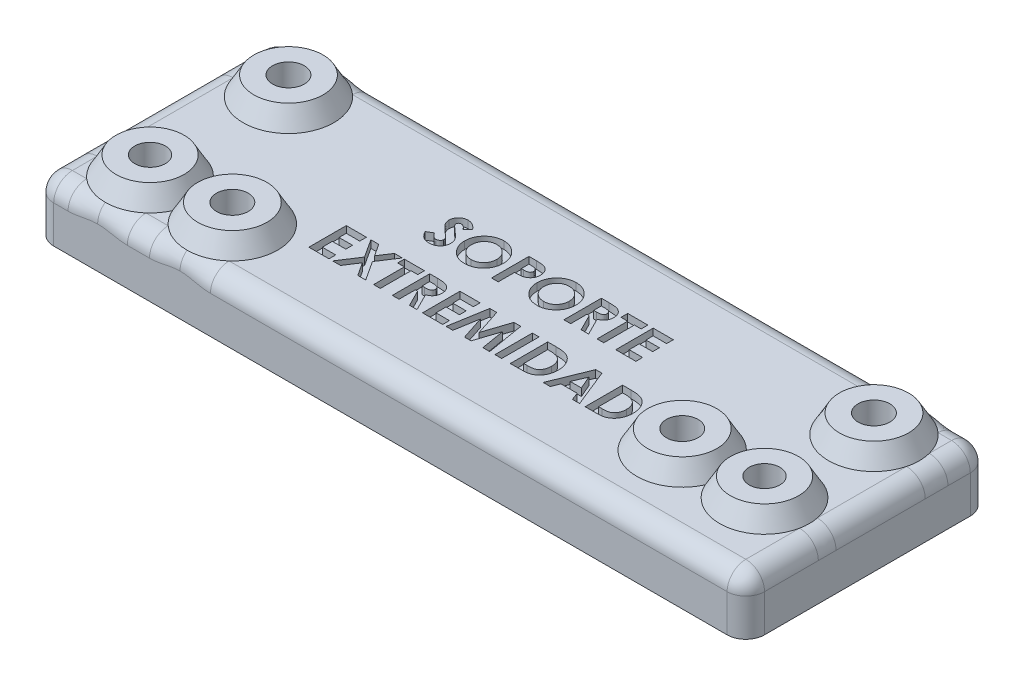
SolidWorks part; units mm, degrees
ref_plane "Front Plane" through (0, 0, 0) normal (0, 0, 1) x (1, 0, 0)
ref_plane "Top Plane" through (0, 0, 0) normal (0, 1, 0) x (1, 0, 0)
ref_plane "Right Plane" through (0, 0, 0) normal (1, 0, 0) x (0, 0, -1)
sketch "Sketch2" plane through (0, 0, 0) normal (0, 1, 0) x (1, 0, 0)
  line L1 (-95, 32.5) -> (95, 32.5)
  line L2 (-95, 32.5) -> (-95, -32.5)
  line L3 (-95, -32.5) -> (95, -32.5)
  line L4 (95, 32.5) -> (95, -32.5)
  line L5 (-95, 32.5) -> (95, -32.5) construction
  line L6 (-95, -32.5) -> (95, 32.5) construction
  point P0 (0, 0)
  dimension "D1" = 190
  dimension "D2" = 65
extrude "Boss-Extrude1" add sketch "Sketch2" along normal blind 15
sketch "Sketch4" plane through (0, 15, -21) normal (0, -1, 0) x (1, 0, 0)
  line L0 (56.25, 31.75) -> (78.25, 31.75) construction
  line L1 (-95, -11.5) -> (-95, 53.5) construction
  line L2 (64.6, -11.5) -> (64.6, 53.5) construction
  line L3 (95, 53.5) -> (95, -11.5) construction
  line L4 (-56.25, 39.5) -> (-78.25, 39.5) construction
  line L5 (95, -11.5) -> (-95, -11.5) construction
  line L6 (95, 42.25) -> (-95, 42.25) construction
  line L7 (-95, 53.5) -> (95, 53.5) construction
  line L8 (-95, -11.5) -> (95, 53.5) construction
  line L9 (78.25, 21) -> (-78.25, 21) construction
  line L10 (-48.6, -11.5) -> (-48.6, 53.5) construction
  line L12 (-64.6, -11.5) -> (-64.6, 53.5) construction
  line L13 (-78.25, 2.5) -> (78.25, 2.5) construction
  line L19 (-78.25, 39.5) -> (-78.25, 2.5) construction
  line L20 (78.25, 31.75) -> (78.25, 2.5) construction
  circle A10 centre (-78.25, 2.5) radius 4.25
  circle A11 centre (78.25, 2.5) radius 4.25
  circle A12 centre (56.25, 31.75) radius 4.25
  circle A13 centre (-56.25, 39.5) radius 4.25
  circle A14 centre (78.25, 31.75) radius 4.1
  circle A15 centre (-78.25, 39.5) radius 4.1
  point P6 (-78.25, 21)
  point P16 (0, 21)
  dimension "D1" = 156.5
  dimension "D2" = 7.75
  dimension "D3" = 8.2
  dimension "D4" = 8.5
  dimension "D5" = 37
  dimension "D6" = 10.5
  dimension "D7" = 13.65
  dimension "D8" = 13.65
  dimension "D9" = 29.65
  dimension "D10" = 22
  dimension "D11" = 22
extrude "Cut-Extrude3" cut sketch "Sketch4" along normal up to surface (15 mm away) up to face at (0, 0, 0)
sketch "Sketch5" plane through (0, 15, 0) normal (0, 1, 0) x (1, 0, 0)
  circle A0 centre (78.25, 18.5) radius 4.25 construction
  circle A1 centre (78.25, -10.75) radius 4.1 construction
  circle A2 centre (56.25, -10.75) radius 4.25 construction
  circle A3 centre (-56.25, -18.5) radius 4.25 construction
  circle A4 centre (-78.25, -18.5) radius 4.1 construction
  circle A5 centre (-78.25, 18.5) radius 4.25 construction
  circle A12 centre (78.25, 18.5) radius 4.25
  circle A13 centre (78.25, -10.75) radius 4.1
  circle A14 centre (56.25, -10.75) radius 4.25
  circle A15 centre (-56.25, -18.5) radius 4.25
  circle A16 centre (-78.25, -18.5) radius 4.1
  circle A17 centre (-78.25, 18.5) radius 4.25
  circle A18 centre (78.25, 18.5) radius 9.25
  circle A19 centre (78.25, -10.75) radius 9.1
  circle A20 centre (56.25, -10.75) radius 9.25
  circle A21 centre (-56.25, -18.5) radius 9.25
  circle A22 centre (-78.25, -18.5) radius 9.1
  circle A23 centre (-78.25, 18.5) radius 9.25
  dimension "D1" = 5
extrude "Boss-Extrude2" add sketch "Sketch5" along normal blind 5
chamfer "Chamfer1" distance 5 angle 30 6 edges at (-78.25, 15, 27.6) (-56.25, 15, 27.75) (56.25, 15, 20) (78.25, 15, 19.85) (78.25, 15, -9.25) (-78.25, 15, -9.25) first distance on face at (-78.25, 20, 27.6) first distance on face at (-56.25, 20, 27.75) first distance on face at (56.25, 20, 20) first distance on face at (78.25, 20, 19.85) first distance on face at (78.25, 20, -9.25) first distance on face at (-78.25, 20, -9.25)
sketch "Sketch6" plane through (0, 0, 0) normal (0, -1, 0) x (1, 0, 0)
  line L0 (-56.25, 26.121) -> (-56.25, 10.879) construction
  line L1 (-56.25, 10.879) -> (-49.65, 14.6895)
  line L2 (-49.65, 14.6895) -> (-49.65, 22.3105)
  line L3 (-49.65, 22.3105) -> (-56.25, 26.121)
  line L4 (-56.25, 26.121) -> (-62.85, 22.3105)
  line L5 (-62.85, 22.3105) -> (-62.85, 14.6895)
  line L6 (-62.85, 14.6895) -> (-56.25, 10.879)
  line L7 (-78.25, -10.879) -> (-78.25, -26.121) construction
  line L14 (-78.25, -26.121) -> (-71.65, -22.3105)
  line L21 (-71.65, -22.3105) -> (-71.65, -14.6895)
  line L28 (-71.65, -14.6895) -> (-78.25, -10.879)
  line L35 (-78.25, -10.879) -> (-84.85, -14.6895)
  line L36 (-84.85, -14.6895) -> (-84.85, -22.3105)
  line L37 (-84.85, -22.3105) -> (-78.25, -26.121)
  line L38 (56.25, 3.129) -> (62.85, 6.9395)
  line L39 (62.85, 6.9395) -> (62.85, 14.5605)
  line L40 (62.85, 14.5605) -> (56.25, 18.371)
  line L41 (56.25, 18.371) -> (49.65, 14.5605)
  line L42 (49.65, 14.5605) -> (49.65, 6.9395)
  line L43 (49.65, 6.9395) -> (56.25, 3.129)
  line L50 (78.25, -26.121) -> (84.85, -22.3105)
  line L51 (84.85, -22.3105) -> (84.85, -14.6895)
  line L52 (84.85, -14.6895) -> (78.25, -10.879)
  line L53 (78.25, -10.879) -> (71.65, -14.6895)
  line L54 (71.65, -14.6895) -> (71.65, -22.3105)
  line L55 (71.65, -22.3105) -> (78.25, -26.121)
  line L56 (56.25, 18.371) -> (56.25, 3.129) construction
  line L57 (78.25, -10.879) -> (78.25, -26.121) construction
  circle A0 centre (-56.25, 18.5) radius 6.6 construction
  circle A1 centre (-78.25, -18.5) radius 6.6 construction
  circle A2 centre (56.25, 10.75) radius 6.6 construction
  circle A4 centre (78.25, -18.5) radius 6.6 construction
  dimension "D1" = 13.2
extrude "Cut-Extrude4" cut sketch "Sketch6" against normal blind 6.5
fillet "Fillet1" radius 5 8 edges at (95, 7.5, -32.5) (95, 7.5, 32.5) (-95, 7.5, -32.5) (-95, 7.5, 32.5) (0, 15, -32.5) (95, 15, 0) (0, 15, 32.5) (-95, 15, 0)
sketch "Sketch7" plane through (0, 15, 0) normal (0, 1, 0) x (1, 0, 0)
  line L0 (63.1719, 0) -> (-63.1719, 0) construction
  line L1 (63.1719, 3.625) -> (-63.1719, 3.625) construction
  text T0 "<b>SOPORTE</b>\r\n<b>EXTREMIDAD</b>" font "Century Gothic" height 10
  point P4 (0, 0)
  dimension "D1" = 3.625
extrude "Cut-Extrude5" cut sketch "Sketch7" against normal blind 2
